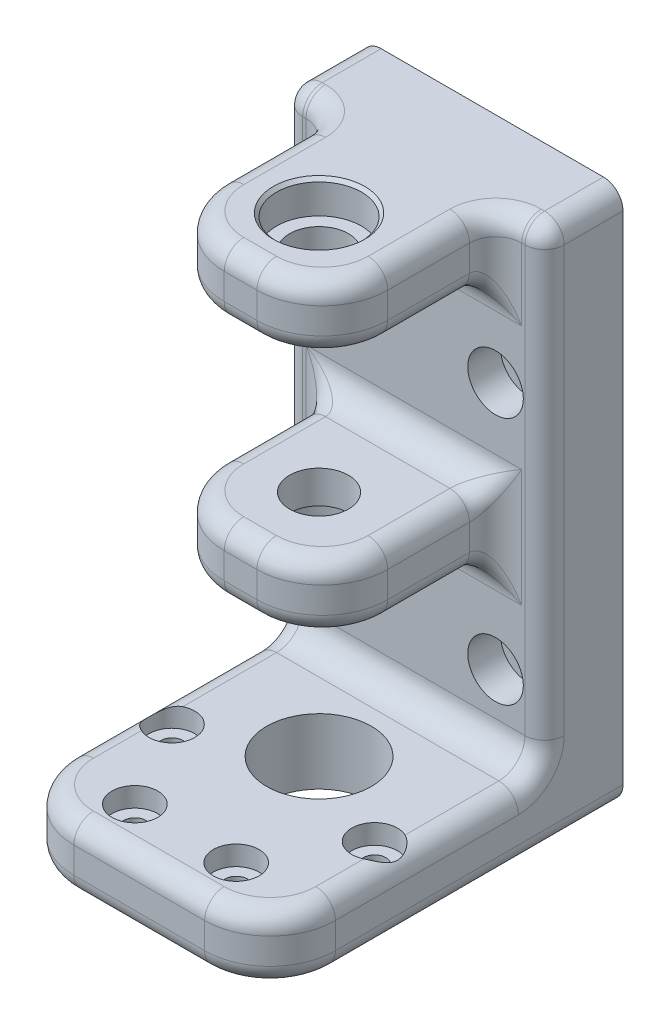
SolidWorks part; units mm, degrees
note: The reader was unsure of these and kept them because the rebuilt part matched: shared geometry of "Croquis3<2>".
ref_plane "Alzado" through (0, 0, 0) normal (1, 0, 0) x (0, 1, 0)
ref_plane "Planta" through (0, 0, 0) normal (0, 0, 1) x (0, 1, 0)
ref_plane "Vista lateral" through (0, 0, 0) normal (0, 1, 0) x (-1, 0, 0)
sketch "Croquis1" plane through (0, 0, 0) normal (0, 1, 0) x (-1, 0, 0)
  line L0 (-12.5, -14.5) -> (-20, -14.5)
  line L2 (-12.5, -14.5) -> (-12.5, 12)
  line L3 (-12.5, 12) -> (12.5, 12)
  line L4 (12.5, -14.5) -> (12.5, 12)
  line L7 (20, -14.5) -> (12.5, -14.5)
  line L8 (20, -14.5) -> (20, -26.5)
  line L9 (20, -26.5) -> (-20, -26.5)
  line L10 (-20, -14.5) -> (-20, -26.5)
  line L11 (0, 0) -> (0, -26.5) construction
  circle A0 centre (0, 0) radius 4.5
  circle A1 centre (0, 0) radius 4.05 construction
  point P0 (0, 0)
  point P16 (0, 12)
  dimension "D3" = 9
  dimension "D1" = 25
  dimension "D5" = 12
  dimension "D6" = 40
  dimension "D2" = 26.5
  dimension "D4" = 12
extrude "Saliente-Extruir1" add sketch "Croquis1" along normal mid plane 47
sketch "Croquis2" plane through (0, 0, 12) normal (0, 0, 1) x (1, 0, 0)
  line L0 (12.5, 23.5) -> (12.5, -23.5) construction
  line L1 (12.5, 13.5) -> (-12.5, 13.5)
  line L2 (12.5, 13.5) -> (12.5, -13.5)
  line L3 (12.5, -13.5) -> (-12.5, -13.5)
  line L4 (-12.5, 13.5) -> (-12.5, -13.5)
  line L5 (-12.5, 23.5) -> (-12.5, -23.5) construction
  line L8 (-12.5, -23.5) -> (12.5, -23.5) construction
  line L9 (-12.5, 23.5) -> (12.5, 23.5) construction
  dimension "D1" = 10
  dimension "D2" = 10
extrude "Cortar-Extruir1" cut sketch "Croquis2" against normal up to surface (26.5 mm away) up to face at (-16.25, 0, -14.5)
fillet "Redondeo1" radius 10 4 edges at (-12.5, 18.5, 12) (12.5, 18.5, 12) (-12.5, -18.5, 12) (12.5, -18.5, 12)
sketch "Croquis3" plane through (0, 0, 0) normal (0, 1, 0) x (-1, 0, 0)
  circle A0 centre (0, 0) radius 6.5
  dimension "D1" = 13
extrude "Cortar-Extruir2" cut sketch "Croquis3" along normal blind 5 from surface at -23.5 starting at face at (0, -23.5, -7.8858)
sketch "Croquis4" plane through (0, 0, -14.5) normal (0, 0, 1) x (0, 1, 0)
  line L0 (0, 12.5) -> (0, -12.5) construction
  line L2 (0, 12.5) -> (-38, 12.5) construction
  line L4 (-13.5, 12.5) -> (-23.5, 12.5) construction
  line L7 (-38, 12.5) -> (-38, -12.5) construction
  point P1 (0, -12.5)
  point P20 (-38, 12.5)
  point P23 (0, 12.5)
  point P37 (-38, -12.5)
  dimension "D1" = 0
  dimension "D3" = 38
extrude "Cortar-Extruir3" cut sketch "Croquis3<2>" against normal blind 5 from surface at 23.5 starting at face at (0, 23.5, -7.8858)
sketch "Croquis3<2>" plane through (0, 0, 0) normal (0, 1, 0) x (-1, 0, 0) same geometry as "Croquis3"
sketch "Croquis6" plane through (0, -23.5, 0) normal (0, -1, 0) x (1, 0, 0)
  line L1 (-20, -14.5) -> (20, -14.5)
  line L2 (-20, -14.5) -> (-20, -26.5)
  line L3 (-20, -26.5) -> (20, -26.5)
  line L4 (20, -14.5) -> (20, -26.5)
extrude "Saliente-Extruir2" add sketch "Croquis6" along normal blind 25
sketch "Croquis7" plane through (0, -48.5, 0) normal (0, -1, 0) x (1, 0, 0)
  line L0 (20, -26.5) -> (20, -14.5) construction
  line L1 (-20, -26.5) -> (20, -26.5)
  line L2 (-20, -26.5) -> (-20, 17.5)
  line L3 (-10, 27.5) -> (10, 27.5)
  line L4 (20, -26.5) -> (20, 17.5)
  line L5 (0, 7) -> (15.5, 7) construction
  line L6 (0, 7) -> (7.75, 20.4234) construction
  arc A0 (10, 27.5) -> (20, 17.5) centre (10, 17.5) cw
  arc A1 (-20, 17.5) -> (-10, 27.5) centre (-10, 17.5) cw
  circle A3 centre (0, 7) radius 15.5 construction
  circle A4 centre (0, 0) radius 8
  point P9 (20, 27.5)
  point P16 (15.5, 7)
  point P20 (7.75, 20.4234)
  point P21 (-7.75, 20.4234)
  point P22 (-15.5, 7)
  dimension "D2" = 10
  dimension "D3" = 7
  dimension "D4" = 31
  dimension "D7" = 16
  dimension "D1" = 54
  dimension "D6" = 60
  dimension "D5" = 4
extrude "Saliente-Extruir3" add sketch "Croquis7" along normal blind 10
sketch "Croquis8" plane through (0, -48.5, 0) normal (0, -1, 0) x (1, 0, 0)
  point P0 (15.5, 7)
  point P2 (7.75, 20.4234)
  point P4 (-7.75, 20.4234)
  point P6 (-15.5, 7)
hole_wizard "Refrentado para tornillo con cabeza troncocónica de M32" positions "Croquis8" profile "Croquis9" counterbore size "M3" standard "Ansi Metric" end condition through all
sketch "Croquis9" plane through (15.5, -48.5, 7) normal (1, 0, 0) x (0, 0, 1)
  line L0 (0, 0) -> (0, 10)
  line L1 (0, 10) -> (1.7, 10)
  line L3 (1.7, 10) -> (1.7, 3)
  line L4 (1.7, 3) -> (3.5, 3)
  line L5 (3.5, 3) -> (3.5, 0)
  line L7 (3.5, 0) -> (0, 0)
  line L11 (0, -6.35) -> (0, 107.95) construction
  dimension "Diámetro de taladro hasta el siguiente" = 3.4
  dimension "Profundidad de taladro hasta el siguiente" = 10
  dimension "Diámetro de refrentado" = 7
  dimension "Profundidad de refrentado" = 3
hole_wizard "Refrentado para tornillo con cabeza troncocónica de M41" positions "Croquis4" profile "Croquis5" counterbore size "M4" standard "Ansi Metric"
sketch "Croquis5" plane through (12.5, 0, -14.5) normal (1, 0, 0) x (0, -1, 0)
  line L0 (0, 0) -> (0, 16.3519)
  line L1 (0, 16.3519) -> (2.25, 15)
  line L2 (2.25, 15) -> (2.25, 5)
  line L3 (2.25, 5) -> (4.25, 5)
  line L4 (4.25, 5) -> (4.25, 0)
  line L5 (4.25, 0) -> (0, 0)
  line L10 (0, 16.3519) -> (-2.25, 15) construction
  line L11 (0, -6.35) -> (0, 107.95) construction
  dimension "Diámetro de taladro" = 4.5
  dimension "Profundidad de taladro" = 15
  dimension "Diámetro de refrentado" = 8.5
  dimension "Profundidad de refrentado" = 5
  dimension "Ángulo de perforador" = 118
fillet "Redondeo3" radius 4 8 edges at (0, 13.5, -14.5) (0, -23.5, -14.5) (0, -13.5, -14.5) (0, -48.5, -14.5) (-12.5, -18.5, -14.5) (-12.5, 18.5, -14.5) (12.5, 18.5, -14.5) (12.5, -18.5, -14.5)
fillet "Redondeo4" radius 3 46 edges at (20, -58.5, -4.5) (17.0711, -58.5, 24.5711) (0, -58.5, 27.5) (-17.0711, -58.5, 24.5711) (-18.25, 23.5, -14.5) (-13.6716, 23.5, -13.3284) (-12.5, 23.5, -4.25) (-9.5711, 23.5, 9.0711) (0, 23.5, 12) (9.5711, 23.5, 9.0711) (18.25, 23.5, -14.5) (13.6716, 23.5, -13.3284) (13.6716, 12.3284, -13.3284) (-13.6716, 12.3284, -13.3284) (-12.5, 13.5, -4.25) (-9.5711, 13.5, 9.0711) (0, 13.5, 12) (9.5711, 13.5, 9.0711) (-13.6716, -24.6716, -13.3284) (-12.5, -23.5, -4.25) (-9.5711, -23.5, 9.0711) (0, -23.5, 12) (9.5711, -23.5, 9.0711) (13.6716, -24.6716, -13.3284) (13.6716, -12.3284, -13.3284) (-13.6716, -12.3284, -13.3284) (-12.5, -13.5, -4.25) (-9.5711, -13.5, 9.0711) (0, -13.5, 12) (9.5711, -13.5, 9.0711) (20, -10.5, -14.5) (20, -47.3284, -13.3284) (-20, -10.5, -14.5) (-20, -47.3284, -13.3284) (-20, -48.5, 3.5) (-17.0711, -48.5, 24.5711) (0, -48.5, 27.5) (17.0711, -48.5, 24.5711) (-20, -58.5, -4.5) (-20, 23.5, -20.5) (20, 23.5, -20.5) (12.5, 23.5, -4.25) (12.5, 13.5, -4.25) (12.5, -23.5, -4.25) (12.5, -13.5, -4.25) (20, -48.5, 3.5)
chamfer "Chaflán1" distance 0.5 angle 45 2 edges at (0, -23.5, -6.5) (0, 23.5, -6.5)
equation "\"ancho\"= 25"
equation "\"D1@Croquis1\"=\"ancho\""
equation "\"altura_total\"=30"
equation "\"altura_eje_motor\"=26.5"
equation "\"d_eje_motor\"=9"
equation "\"D3@Croquis1\"=\"d_eje_motor\""
equation "\"esp\"=10"
equation "\"D1@Saliente-Extruir1\"=\"esp\"*2+\"ancho_polea\"+\"sep_polea\"*2"
equation "\"D1\"= \"esp\""
equation "\"D1@Croquis2\"=\"esp\""
equation "\"D2@Croquis2\"=\"D1@Croquis2\""
equation "\"D6@Croquis1\"=\"D1@Croquis1\"+15"
equation "\"d_rodamiento\"=13"
equation "\"D1@Croquis3\"=\"d_rodamiento\""
equation "\"ancho_polea\"= 21"
equation "\"sep_polea\"= 3"
equation "\"sep_acople\"=25"
equation "\"D1@Saliente-Extruir2\"=\"sep_acople\""
equation "\"esp_sop_motor\"=10"
equation "\"D1@Saliente-Extruir3\"=\"esp_sop_motor\""
equation "\"D2@Croquis1\"=\"altura_eje_motor\""
